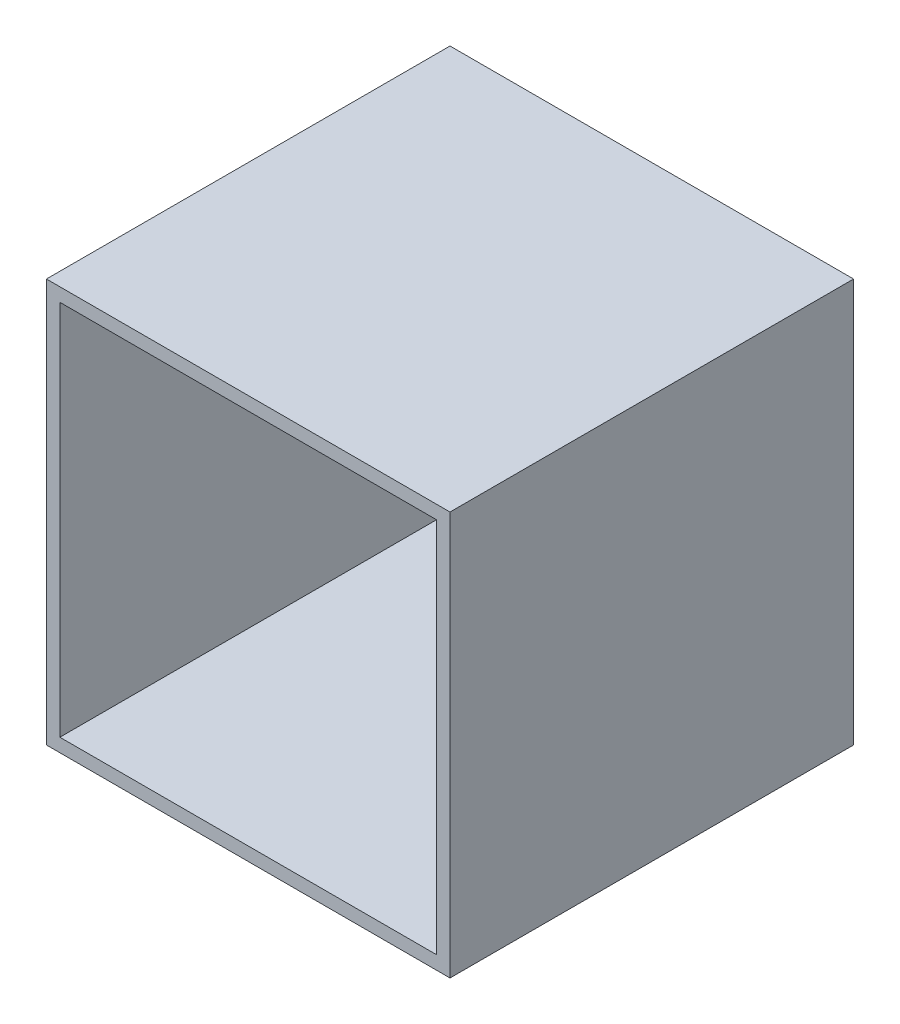
SolidWorks part; units mm, degrees
ref_plane "Front Plane" through (0, 0, 0) normal (0, 0, 1) x (1, 0, 0)
ref_plane "Top Plane" through (0, 0, 0) normal (0, 1, 0) x (1, 0, 0)
ref_plane "Right Plane" through (0, 0, 0) normal (1, 0, 0) x (0, 0, -1)
sketch "Sketch1" plane through (0, 0, 0) normal (0, 1, 0) x (1, 0, 0)
  line L1 (-38.1, -38.1) -> (38.1, -38.1)
  line L2 (-38.1, -38.1) -> (-38.1, 38.1)
  line L3 (-38.1, 38.1) -> (38.1, 38.1)
  line L4 (38.1, -38.1) -> (38.1, 38.1)
  line L5 (-38.1, -38.1) -> (38.1, 38.1) construction
  line L6 (-38.1, 38.1) -> (38.1, -38.1) construction
  point P0 (0, 0)
  dimension "D1" = 76.2
  dimension "D2" = 76.2
extrude "box" add sketch "Sketch1" along normal blind 76.2
shell "hollow it" thickness 2.54 removed face at (0, 38.1, 38.1)
sketch "Sketch2" plane through (0, 0, -38.1) normal (0, 0, -1) x (-1, 0, 0)
  line L0 (-38.1, 76.2) -> (38.1, 76.2) construction
  line L1 (-27.94, 69.85) -> (-20.32, 69.85)
  line L2 (-27.94, 69.85) -> (-27.94, 6.35)
  line L3 (-27.94, 6.35) -> (-20.32, 6.35)
  line L4 (-20.32, 69.85) -> (-20.32, 6.35)
  line L6 (-38.1, 76.2) -> (-38.1, 0) construction
  dimension "D1" = 7.62
  dimension "D2" = 63.5
  dimension "D3" = 6.35
  dimension "D4" = 10.16
extrude "slider track" cut sketch "Sketch2" against normal up to surface (2.54 mm away) up to face at (0, 38.1, -35.56)
sketch "Sketch4" plane through (0, 0, -38.1) normal (0, 0, -1) x (-1, 0, 0)
  line L0 (-38.1, 76.2) -> (38.1, 76.2) construction
  circle A0 centre (0, 63.5) radius 6.35
  dimension "D1" = 12.7
  dimension "D2" = 12.7
extrude "button large ring" cut sketch "Sketch4" against normal blind 1.27
sketch "Sketch5" plane through (0, 0, -36.83) normal (0, 0, -1) x (-1, 0, 0)
  circle A0 centre (0, 63.5) radius 3.556
  circle A1 centre (0, 63.5) radius 6.35 construction
  dimension "D2" = 7.112
  dimension "D1" = 0
extrude "button small hole" cut sketch "Sketch5" against normal blind 1.27
sketch "Sketch6" plane through (0, 0, -38.1) normal (0, 0, -1) x (-1, 0, 0)
  line L0 (-3.2977, 25.4) -> (-3.2977, 31.75)
  line L1 (-3.2977, 31.75) -> (3.0523, 31.75)
  line L2 (3.0523, 31.75) -> (3.0523, 25.4)
  line L3 (3.0523, 25.4) -> (9.4023, 25.4)
  line L4 (9.4023, 25.4) -> (9.4023, 19.05)
  line L5 (9.4023, 19.05) -> (3.0523, 19.05)
  line L6 (3.0523, 19.05) -> (3.0523, 12.7)
  line L7 (3.0523, 12.7) -> (-3.2977, 12.7)
  line L8 (-3.2977, 12.7) -> (-3.2977, 19.05)
  line L9 (-3.2977, 19.05) -> (-9.6477, 19.05)
  line L10 (-9.6477, 19.05) -> (-9.6477, 25.4)
  line L11 (-9.6477, 25.4) -> (-3.2977, 25.4)
  line L12 (-38.1, 0) -> (38.1, 0) construction
  dimension "D1" = 6.35
  dimension "D2" = 6.35
  dimension "D3" = 6.35
  dimension "D4" = 6.35
  dimension "D5" = 6.35
  dimension "D6" = 6.35
  dimension "D7" = 6.35
  dimension "D8" = 6.35
  dimension "D9" = 6.35
  dimension "D10" = 12.7
extrude "dpad large shape" cut sketch "Sketch6" against normal blind 1.27
sketch "Sketch7" plane through (0, 0, -36.83) normal (0, 0, -1) x (-1, 0, 0)
  line L0 (-3.2977, 25.4) -> (-9.6477, 25.4) construction
  line L1 (-9.6477, 25.4) -> (-9.6477, 19.05) construction
  line L2 (3.0523, 12.7) -> (3.0523, 19.05) construction
  line L3 (-3.2977, 12.7) -> (3.0523, 12.7) construction
  line L4 (3.0523, 19.05) -> (9.4023, 19.05) construction
  line L5 (9.4023, 19.05) -> (9.4023, 25.4) construction
  line L6 (3.0523, 25.4) -> (3.0523, 31.75) construction
  line L7 (-3.2977, 31.75) -> (-3.2977, 25.4) construction
  line L8 (3.0523, 31.75) -> (-3.2977, 31.75) construction
  circle A0 centre (-0.1227, 28.575) radius 1.397
  circle A1 centre (6.2273, 22.225) radius 1.397
  circle A2 centre (-0.1227, 15.875) radius 1.397
  circle A3 centre (-6.4727, 22.225) radius 1.397
  point P12 (3.0523, 15.875)
  point P17 (6.2273, 19.05)
  dimension "D3" = 2.794
  dimension "D6" = 2.794
  dimension "D9" = 2.794
  dimension "D13" = 2.794
  dimension "D1" = 3.175
  dimension "D2" = 3.175
  dimension "D4" = 3.175
  dimension "D5" = 3.175
  dimension "D7" = 3.175
  dimension "D8" = 3.175
  dimension "D10" = 3.175
  dimension "D11" = 3.175
  dimension "D12" = 3.175
extrude "dpad tiny holes" cut sketch "Sketch7" against normal blind 1.27
sketch "Sketch8" plane through (0, 0, -38.1) normal (0, 0, -1) x (-1, 0, 0)
  line L0 (38.1, 76.2) -> (38.1, 0) construction
  circle A0 centre (21.336, 43.0507) radius 12.7
  dimension "D1" = 25.4
  dimension "D2" = 16.764
extrude "dial large ring" cut sketch "Sketch8" against normal blind 1.27
ref_point "dial center"
sketch "Sketch9" plane through (0, 0, -36.83) normal (0, 0, -1) x (-1, 0, 0)
  circle A0 centre (21.336, 43.0507) radius 5.08
  dimension "D1" = 10.16
extrude "dial small hole" cut sketch "Sketch9" against normal blind 1.27
sketch "Sketch10" plane through (0, 73.66, 0) normal (0, -1, 0) x (1, 0, 0)
  line L0 (35.56, -35.56) -> (-35.56, -35.56) construction
  line L1 (-3.81, -35.56) -> (3.81, -35.56)
  line L2 (-3.81, -35.56) -> (-3.81, 15.24)
  line L3 (-3.81, 15.24) -> (3.81, 15.24)
  line L4 (3.81, -35.56) -> (3.81, 15.24)
  line L5 (-35.56, -35.56) -> (-35.56, 38.1) construction
  line L6 (35.56, 38.1) -> (35.56, -35.56) construction
  dimension "D1" = 7.62
  dimension "D2" = 50.8
  dimension "D3" = 31.75
  dimension "D4" = 31.75
extrude "linkage track" add sketch "Sketch10" along normal blind 5.08
sketch "Sketch11" plane through (0, 0, 15.24) normal (0, 0, 1) x (1, 0, 0)
  line L0 (-1.778, 68.58) -> (-1.778, 70.104)
  line L1 (-3.81, 68.58) -> (3.81, 68.58) construction
  line L2 (-1.778, 70.104) -> (-2.794, 70.104)
  line L3 (-2.794, 70.104) -> (-2.794, 73.66)
  line L4 (3.81, 73.66) -> (-3.81, 73.66) construction
  line L5 (-2.794, 73.66) -> (2.794, 73.66)
  line L6 (-35.56, 73.66) -> (35.56, 73.66) construction
  line L7 (2.794, 73.66) -> (2.794, 70.104)
  line L8 (2.794, 70.104) -> (1.778, 70.104)
  line L9 (1.778, 70.104) -> (1.778, 68.58)
  line L10 (1.778, 68.58) -> (-1.778, 68.58)
  dimension "D1" = 1.016
  dimension "D2" = 1.016
  dimension "D3" = 2.032
  dimension "D4" = 2.032
  dimension "D5" = 1.524
  dimension "D6" = 1.524
extrude "linkage track hole" cut sketch "Sketch11" against normal up to surface (50.8 mm away) up to face at (24.13, 38.1, -35.56)
sketch "Sketch12" plane through (0, 0, 15.24) normal (0, 0, 1) x (1, 0, 0)
  line L1 (-3.81, 68.58) -> (3.81, 68.58)
  line L2 (-3.81, 68.58) -> (-3.81, 73.66)
  line L3 (-3.81, 73.66) -> (3.81, 73.66)
  line L4 (3.81, 68.58) -> (3.81, 73.66)
extrude "linkage track cap" add sketch "Sketch12" along normal blind 2.54
